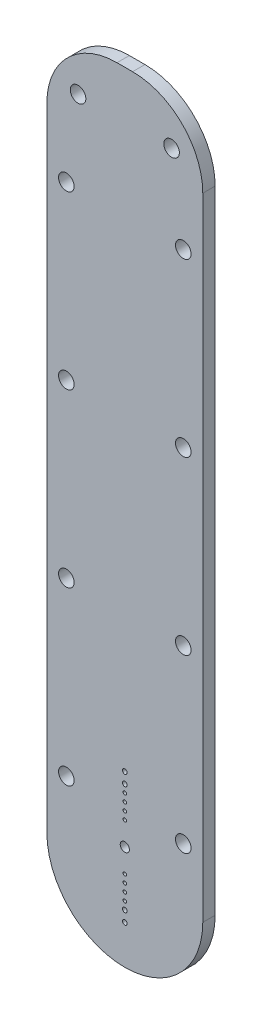
SolidWorks part; units mm, degrees
material "Acrylic (Medium-high impact)"
ref_plane "Front" through (0, 0, 0) normal (0, 0, 1) x (1, 0, 0)
ref_plane "Top" through (0, 0, 0) normal (0, 1, 0) x (1, 0, 0)
ref_plane "Right" through (0, 0, 0) normal (1, 0, 0) x (0, 0, -1)
sketch "Sketch2" plane through (0, 0, 0) normal (0, 0, 1) x (1, 0, 0)
  line L1 (-20, -100) -> (20, -100)
  line L2 (-20, -100) -> (-20, 100)
  line L3 (-20, 100) -> (20, 100)
  line L4 (20, -100) -> (20, 100)
  line L5 (-20, -100) -> (20, 100) construction
  line L6 (-20, 100) -> (20, -100) construction
  point P1 (0, 0)
  dimension "D1" = 200
  dimension "D2" = 40
extrude "Boss-Extrude1" add sketch "Sketch2" along normal blind 3.175
sketch "Sketch3" plane through (0, 0, 0) normal (0, 0, -1) x (-1, 0, 0)
  line L0 (20, -100) -> (-20, -100) construction
  line L1 (1.325, -88.5019) -> (-1.325, -88.5019)
  arc A0 (-1.325, -88.5019) -> (1.325, -88.5019) centre (0, -90) ccw
  dimension "D1" = 4
  dimension "D2" = 10
  dimension "D3" = 2.65
fillet "Fillet1" radius 20 2 edges at (20, -100, 1.5875) (-20, -100, 1.5875)
fillet "Fillet2" radius 18 2 edges at (20, 100, 1.5875) (-20, 100, 1.5875)
sketch "Sketch6" plane through (0, 0, 3.175) normal (0, 0, 1) x (1, 0, 0)
  line L0 (0, -113.8198) -> (0, 113.8198) construction
  line L1 (15, 67) -> (15, 23) construction
  line L2 (15, 23) -> (15, -21) construction
  line L3 (15, -21) -> (15, -65) construction
  line L4 (20, -80) -> (20, 82) construction
  line L5 (-15, -21) -> (-15, -65) construction
  line L6 (-15, 23) -> (-15, -21) construction
  line L7 (-15, 67) -> (-15, 23) construction
  circle A0 centre (15, 67) radius 2
  circle A1 centre (15, -21) radius 2
  circle A2 centre (15, 23) radius 2
  circle A3 centre (15, -65) radius 2
  circle A4 centre (-15, -65) radius 2
  circle A5 centre (-15, 23) radius 2
  circle A6 centre (-15, -21) radius 2
  circle A7 centre (-15, 67) radius 2
  point P11 (0, 0)
  dimension "D1" = 4
  dimension "D2" = 15
  dimension "5" = 5
  dimension "D3" = 15
extrude "Cut-Extrude4" cut sketch "Sketch6" against normal through all
sketch "Sketch7" plane through (0, 0, 3.175) normal (0, 0, 1) x (1, 0, 0)
  line L0 (-30.4029, 88) -> (30.4029, 88) construction
  circle A0 centre (-12, 88) radius 2
  circle A1 centre (12, 88) radius 2
  point P4 (0, 88)
  dimension "D1" = 4
  dimension "D2" = 4
  dimension "D3" = 12
  dimension "D4" = 12
extrude "Cut-Extrude5" cut sketch "Sketch7" against normal through all
sketch "Sketch8" plane through (0, 0, 3.175) normal (0, 0, 1) x (1, 0, 0)
  line L0 (0, -90) -> (0, -49.3452) construction
  circle A0 centre (0, -90) radius 0.6
  circle A1 centre (0, -87.25) radius 0.6
  circle A2 centre (0, -85.25) radius 0.45
  circle A3 centre (0, -83.25) radius 0.45
  circle A4 centre (0, -81.25) radius 0.45
  circle A5 centre (0, -79.25) radius 0.45
  circle A6 centre (0, -67.25) radius 0.45
  circle A7 centre (0, -65.25) radius 0.45
  circle A8 centre (0, -63.25) radius 0.45
  circle A9 centre (0, -61.25) radius 0.45
  circle A10 centre (0, -59.25) radius 0.6
  circle A11 centre (0, -56.5) radius 0.6
  circle A12 centre (0, -73.25) radius 1.175
  dimension "D1" = 1.2
  dimension "D2" = 0.9
  dimension "D14" = 2.35
  dimension "D3" = 2.75
  dimension "D4" = 2
  dimension "D5" = 2
  dimension "D6" = 2
  dimension "D7" = 2
  dimension "D8" = 2.75
  dimension "D9" = 2
  dimension "D10" = 2
  dimension "D11" = 2
  dimension "D12" = 2
  dimension "D13" = 12
  dimension "D15" = 6
extrude "Cut-Extrude6" cut sketch "Sketch8" against normal through all
